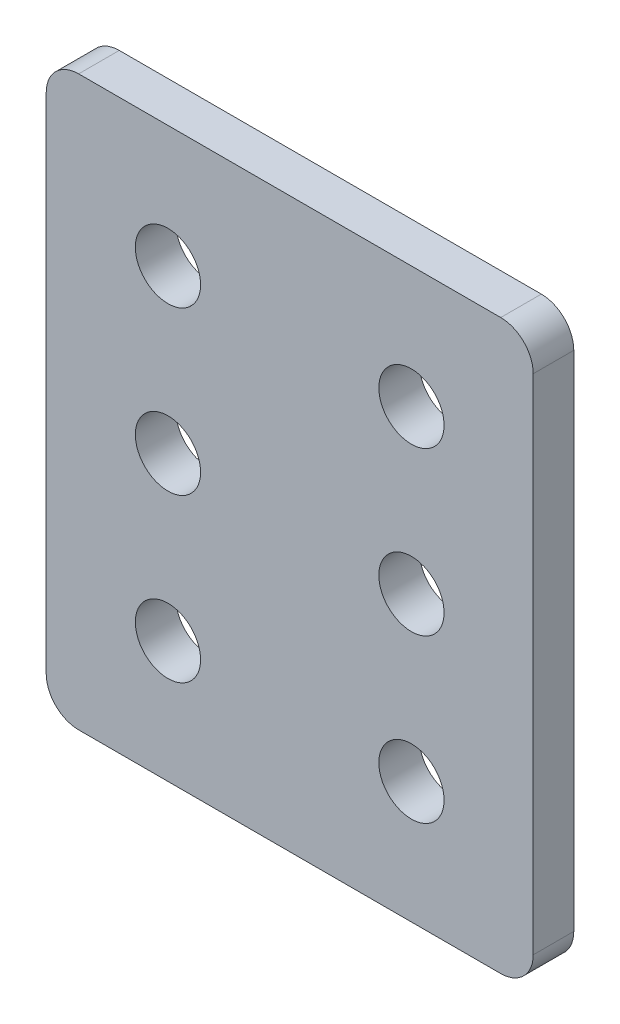
SolidWorks part; units mm, degrees
material "6061-T6 (SS)"
ref_plane "Front Plane" through (0, 0, 0) normal (0, 0, 1) x (1, 0, 0)
ref_plane "Top Plane" through (0, 0, 0) normal (0, 1, 0) x (1, 0, 0)
ref_plane "Right Plane" through (0, 0, 0) normal (1, 0, 0) x (0, 0, -1)
sketch "Sketch1" plane through (0, 0, 0) normal (0, 0, 1) x (1, 0, 0)
  line L0 (-9.525, -12.7) -> (-9.525, 0) construction
  line L5 (-19.05, -22.225) -> (19.05, -22.225)
  line L6 (-19.05, -22.225) -> (-19.05, 22.225)
  line L11 (-19.05, 22.225) -> (19.05, 22.225)
  line L15 (19.05, -22.225) -> (19.05, 22.225)
  line L16 (-19.05, -22.225) -> (19.05, 22.225) construction
  line L17 (-19.05, 22.225) -> (19.05, -22.225) construction
  line L18 (0, 22.225) -> (0, -22.225) construction
  circle A13 centre (-9.525, -12.7) radius 2.5527
  circle A14 centre (-9.525, 0) radius 2.5527
  circle A15 centre (-9.525, 12.7) radius 2.5527
  circle A17 centre (9.525, -12.7) radius 2.5527
  circle A18 centre (9.525, 0) radius 2.5527
  circle A19 centre (9.525, 12.7) radius 2.5527
  point P0 (0, 0)
  point P13 (-14.0177, 12.7)
  dimension "D2" = 12.7
  dimension "D4" = 9.525
  dimension "D5" = 19.05
  dimension "D3" = 9.525
  dimension "D7" = 5.1054
  dimension "D1" = 3
  dimension "D6" = 38.1
extrude "Boss-Extrude1" add sketch "Sketch1" along normal blind 3.175
fillet "Fillet1" radius 2.54 4 edges at (-19.05, 22.225, 1.5875) (-19.05, -22.225, 1.5875) (19.05, -22.225, 1.5875) (19.05, 22.225, 1.5875)
